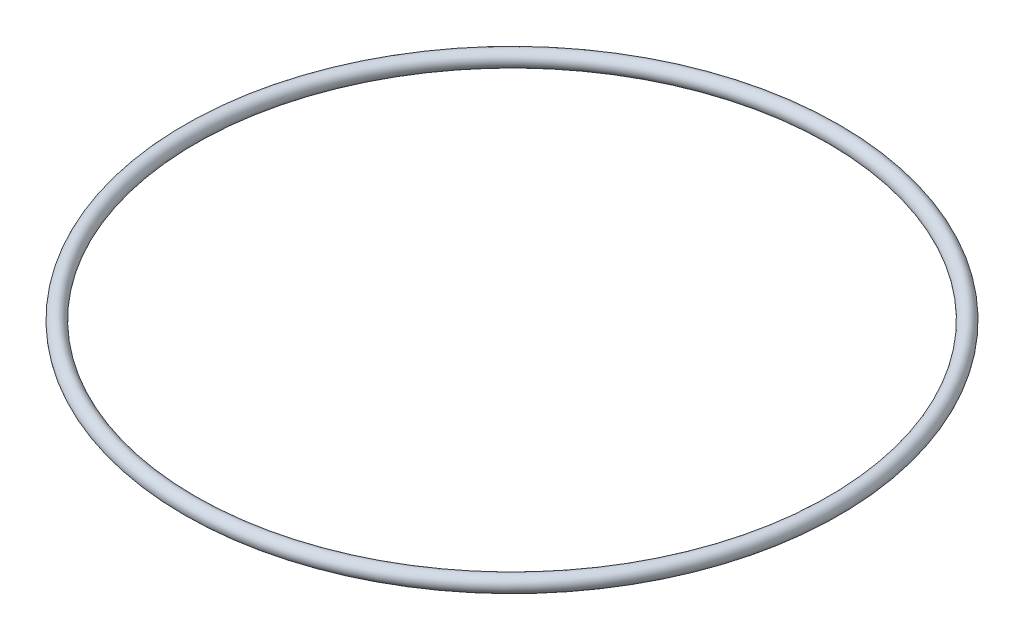
SolidWorks part; units mm, degrees
material "AISI 1020"
ref_plane "Front Plane" through (0, 0, 0) normal (0, 0, 1) x (1, 0, 0)
ref_plane "Top Plane" through (0, 0, 0) normal (0, 1, 0) x (1, 0, 0)
ref_plane "Right Plane" through (0, 0, 0) normal (1, 0, 0) x (0, 0, -1)
sketch "Sketch1" plane through (0, 0, 0) normal (1, 0, 0) x (0, 0, -1)
  line L0 (0, 1.458) -> (0, 0) construction
  line L1 (0, 0) -> (21, 0) construction
  circle A0 centre (21, 0) radius 0.5
  dimension "D1" = 1
  dimension "D2" = 21
revolve "Revolve1" add sketch "Sketch1" angle 360 about L0
ref_axis "Axis1" through (0, -14.8421, 0) along (0, 1, 0)
